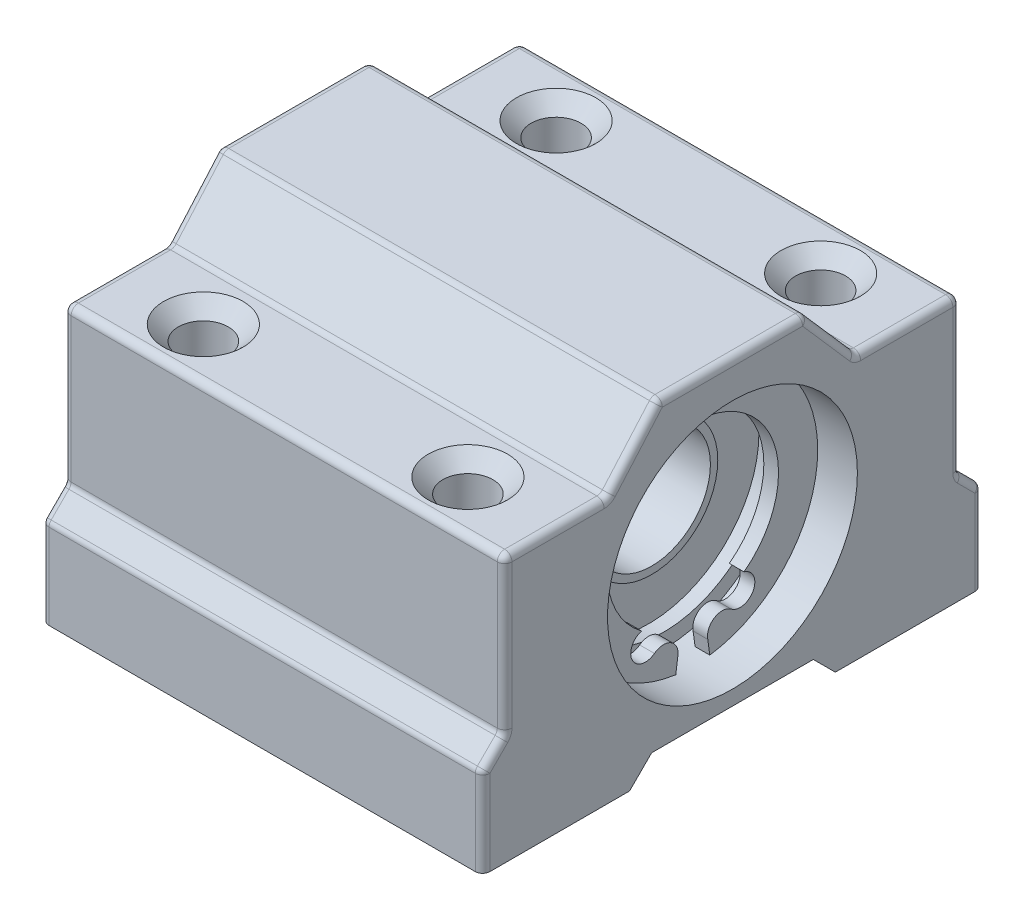
SolidWorks part; units mm, degrees
ref_plane "Front Plane" through (0, 0, 0) normal (0, 0, 1) x (1, 0, 0)
ref_plane "Top Plane" through (0, 0, 0) normal (0, 1, 0) x (1, 0, 0)
ref_plane "Right Plane" through (0, 0, 0) normal (1, 0, 0) x (0, 0, -1)
sketch "Sketch1" plane through (0, 0, 0) normal (1, 0, 0) x (0, 0, -1)
  line L1 (-7, -11) -> (-5.5, -9.5)
  line L2 (-5.5, -9.5) -> (5.5, -9.5)
  line L3 (5.5, -9.5) -> (7, -11)
  line L4 (7, -11) -> (17, -11)
  line L6 (17, -5) -> (15.5, -3.5)
  line L8 (15.5, 7) -> (8.5, 7)
  line L9 (8.5, 7) -> (5, 11)
  line L10 (5, 11) -> (-5, 11)
  line L11 (-5, 11) -> (-8.5, 7)
  line L12 (-8.5, 7) -> (-15.5, 7)
  line L15 (-17, -5) -> (-17, -11)
  line L16 (0, -9.5) -> (0, 11) construction
  line L17 (-16.278, 0) -> (14.0247, 0) construction
  line L18 (-17, -11) -> (-7, -11)
  line L19 (17, -5) -> (17, -11)
  line L20 (-15.5, -3.5) -> (-15.5, 7)
  line L21 (15.5, -3.5) -> (15.5, 7)
  line L22 (-12, 7) -> (-12, -11) construction
  line L23 (-12, -11) -> (12, 7) construction
  line L24 (12, 7) -> (12, -11) construction
  line L25 (-17, -5) -> (-15.5, -3.5)
  line L26 (-8.5, 0) -> (8.5, 0) construction
  circle A0 centre (0, 0) radius 8.5
  circle A1 centre (0, 0) radius 7.5
  circle A2 centre (0, 0) radius 4
  point P18 (0, 11)
  dimension "D12" = 8
  dimension "D1" = 34
  dimension "D2" = 18
  dimension "D3" = 11
  dimension "D5" = 22
  dimension "D6" = 24
  dimension "D4" = 6
  dimension "D7" = 1.5
  dimension "D8" = 10
  dimension "D9" = 1.5
  dimension "D10" = 10
  dimension "D11" = 1
extrude "Boss-Extrude1" add sketch "Sketch1" along normal blind 30 contours L25 L15 L18 L1 L2 L3 L4 L19 L6 L21 L8 L9 L10 L11 L12 L20 A0 region at (0, -10.595, 12)
extrude "Extrude-Thin1" add sketch "Sketch1<4>" along normal blind 24 from offset 0.5 separate body thin contours A2 thin type one direction wall 0.5
sketch "Sketch1<4>" plane through (0, 0, 0) normal (1, 0, 0) x (0, 0, -1) same geometry as "Sketch1"
extrude "Boss-Extrude2" add sketch "Sketch1<5>" along normal blind 23.5 from offset 0.8 contours A1 A2 region at (0, 0, 7.2879)
sketch "Sketch1<5>" plane through (0, 0, 0) normal (1, 0, 0) x (0, 0, -1) same geometry as "Sketch1"
extrude "Boss-Extrude3" add sketch "Sketch1<6>" along normal blind 25 from offset 0.3 contours A0 A1 region at (0, 0, 8.2596)
sketch "Sketch1<6>" plane through (0, 0, 0) normal (1, 0, 0) x (0, 0, -1) same geometry as "Sketch1"
ref_plane "Plane1" through (25.3, 0, 0) normal (1, 0, 0) x (0, 0, -1)
sketch "Sketch3" plane through (25.3, 0, 0) normal (1, 0, 0) x (0, 0, -1)
  line L0 (0, 0) -> (0, -50000) construction
  line L1 (-1.0206, -7.4302) -> (-1.1567, -8.4209)
  line L2 (1.0206, -7.4302) -> (1.1567, -8.4209)
  circle A0 centre (0, 0) radius 8.5 construction
  arc A1 (1.1567, -8.4209) -> (-1.1567, -8.4209) centre (0, 0) ccw
  circle A2 centre (0, 0) radius 7.5 construction
  arc A3 (0, -7.5) -> (1.0206, -7.4302) centre (0, 0) ccw
  arc A4 (-1.0206, -7.4302) -> (-2.611, -6.4368) centre (-2, -7.2284) ccw
  circle A5 centre (-2, -7.2284) radius 0.25
  arc A6 (-2.2398, -7.1577) -> (-1.758, -7.2911) centre (0, 0) ccw
  arc A7 (-2.611, -6.4368) -> (-3.4848, -4.6803) centre (-3.2221, -5.6452) cw
  arc A8 (2.611, -6.4368) -> (3.4848, -4.6803) centre (3.2221, -5.6452) ccw
  circle A10 centre (2, -7.2284) radius 0.25
  arc A11 (1.0206, -7.4302) -> (2.611, -6.4368) centre (2, -7.2284) cw
  arc A13 (3.4848, -4.6803) -> (-3.4848, -4.6803) centre (0, 0) ccw
  dimension "D1" = 0.5
  dimension "D2" = 2
  dimension "D3" = 1
  dimension "D4" = 2
extrude "Boss-Extrude4" add sketch "Sketch3" along normal blind 1 from offset 1 contours A11 A8 A13 A7 A4 L1 A1 L2
fillet "Fillet1" radius 0.5 32 edges at (15, -3.5, -15.5) (15, -3.5, 15.5) (15, -5, 17) (15, -5, -17) (15, 7, -8.5) (15, 7, 8.5) (15, 11, 5) (15, 11, -5) (15, 7, -15.5) (15, 7, 15.5) (30, 9, -6.75) (30, 9, 6.75) (30, 1.75, 15.5) (0, -4.25, 16.25) (0, 9, 6.75) (30, -4.25, -16.25) (30, -8, -17) (30, 1.75, -15.5) (30, 11, 0) (30, 7, -12) (30, 7, 12) (30, -4.25, 16.25) (30, -8, 17) (0, -8, -17) (0, -4.25, -16.25) (0, 1.75, -15.5) (0, 9, -6.75) (0, 7, -12) (0, 11, 0) (0, -8, 17) (0, 1.75, 15.5) (0, 7, 12)
sketch "Sketch4" plane through (0, -11, 0) normal (0, -1, 0) x (1, 0, 0)
  line L0 (15, 17) -> (15, -17) construction
  line L1 (29.5, 17) -> (0.5, 17) construction
  line L2 (29.5, -17) -> (0.5, -17) construction
  line L4 (-4.9444, 12) -> (27.0918, 12) construction
  line L6 (0, 0) -> (36.1646, 0) construction
  circle A0 centre (6, 12) radius 1.7
  circle A1 centre (24, 12) radius 1.7
  circle A2 centre (24, -12) radius 1.7
  circle A3 centre (6, -12) radius 1.7
  dimension "D2" = 3.4
  dimension "D1" = 12
  dimension "D3" = 18
extrude "Cut-Extrude3" cut sketch "Sketch4" against normal through all
chamfer "Chamfer1" distance 1 angle 45 6 edges at (24, 7, -13.7) (6, 7, -13.7) (6, 7, 10.3) (24, 7, 10.3) (24, -11, 13.7) (6, -11, 10.3)
equation "\"D1@Boss-Extrude2\"= \"D1@Extrude-Thin1\" - 0.5"
equation "\"D1@Boss-Extrude3\"= \"D1@Boss-Extrude1\" - 5"
equation "\"D1@Sketch4\"= \"D6@Sketch1\" / 2"
